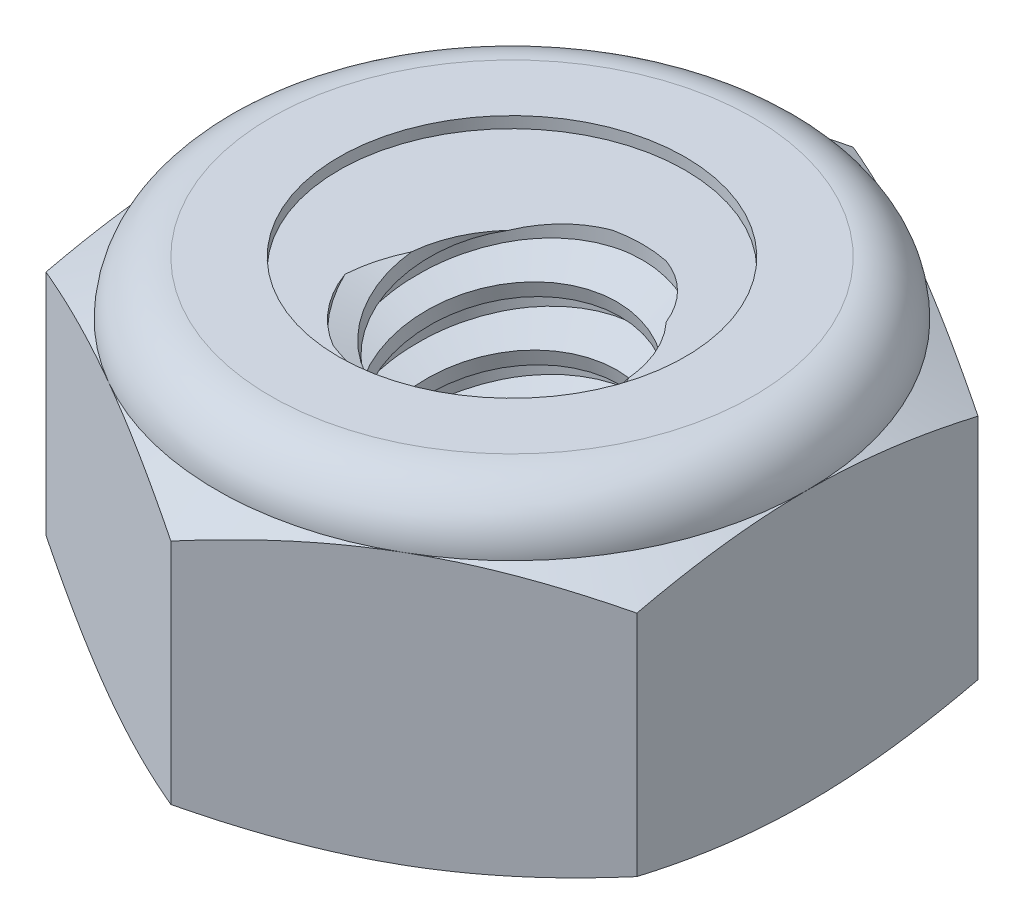
SolidWorks part; units mm, degrees
ref_plane "Front" through (0, 0, 0) normal (0, 0, 1) x (1, 0, 0)
ref_plane "Top" through (0, 0, 0) normal (0, 1, 0) x (1, 0, 0)
ref_plane "Right" through (0, 0, 0) normal (1, 0, 0) x (0, 0, -1)
sketch "Sketch1" plane through (0, 0, 0) normal (0, 1, 0) x (1, 0, 0)
  line L1 (0, 4.5827) -> (-3.9688, 2.2914)
  line L2 (-3.9688, 2.2914) -> (-3.9688, -2.2914)
  line L3 (-3.9688, -2.2914) -> (0, -4.5827)
  line L4 (0, -4.5827) -> (3.9687, -2.2914)
  line L5 (3.9687, -2.2914) -> (3.9687, 2.2914)
  line L6 (3.9687, 2.2914) -> (0, 4.5827)
  circle A0 centre (0, 0) radius 3.9688 construction
  dimension "Hex Flats" = 7.9375
extrude "Extrude1" add sketch "Sketch1" along normal blind 4.3656
sketch "Sketch2" plane through (0, 0, 0) normal (1, 0, 0) x (0, 0, -1)
  line L0 (-1.7526, 0) -> (-1.7526, 4.3656) construction
  line L1 (0, 0) -> (1.7526, 0)
  line L2 (0, 0) -> (0, 4.3656)
  line L3 (0, 4.3656) -> (1.7526, 4.3656)
  line L4 (1.7526, 0) -> (1.7526, 4.3656)
  line L5 (-2.2914, 4.3656) -> (2.2914, 4.3656) construction
  line L7 (0, -1.7526) -> (0, 0) construction
  dimension "Thread Dia" = 3.5052
revolve "Revolve1" add sketch "Sketch2" angle 360 about L7
sketch "Sketch3" plane through (0, 0, 0) normal (1, 0, 0) x (0, 0, -1)
  line L0 (1.7526, 4.3656) -> (-1.7526, 4.3656) construction
  line L1 (-1.7526, 4.3656) -> (-1.7526, 3.5719) construction
  line L2 (-1.7526, 3.5719) -> (1.7526, 4.3656) construction
  line L3 (1.7526, 4.3656) -> (1.7745, 4.2689) construction
  line L4 (1.7745, 4.2689) -> (1.9279, 3.5915)
  line L5 (1.9279, 3.5915) -> (1.4541, 3.7385)
  line L6 (1.4541, 3.7385) -> (1.4103, 3.932)
  line L7 (1.4103, 3.932) -> (1.7745, 4.2689)
  line L8 (1.4322, 3.8353) -> (1.8512, 3.9302) construction
  line L9 (1.7526, 4.3656) -> (1.7526, 3.9078) construction
  line L10 (1.7526, 3.9078) -> (-1.7526, 3.1141) construction
  line L11 (-1.7526, 3.1141) -> (-1.7526, 3.5719) construction
  line L12 (-0.1935, 4.3656) -> (0.1935, 2.6563) construction
  line L13 (-1.7526, 0) -> (-1.7526, 4.3656) construction
  line L14 (0, 4.3656) -> (1.7526, 4.3656) construction
  line L15 (1.7526, 0) -> (1.7526, 4.3656) construction
  point P13 (0, 3.511)
  dimension "D1" = 0.0992
  dimension "D2" = 0.1984
  dimension "Thread Pitch" = 0.7937
  dimension "D4" = 60
  dimension "D5" = 0.7937
revolve "Cut-Revolve1" cut sketch "Sketch3" angle 360 about L12
pattern_linear "LPattern1" count 6 spacing 0.7937 along (0, -1, 0) count 2 spacing 0.7937 along (0, 1, 0) of "Cut-Revolve1"
sketch "Sketch4" plane through (0, 0, 0) normal (1, 0, 0) x (0, 0, -1)
  line L0 (0, 4.3656) -> (1.7526, 4.3656)
  line L1 (1.7526, 4.3656) -> (1.4103, 4.206)
  line L2 (1.4103, 4.206) -> (1.4103, 0.1596)
  line L3 (1.4103, 0.1596) -> (1.7526, 0)
  line L4 (1.7526, 0) -> (0, 0)
  line L5 (0, 0) -> (0, 4.3656)
  line L6 (1.7526, 0) -> (1.7526, 4.3656) construction
  line L7 (0, 4.3656) -> (1.7526, 4.3656) construction
  line L8 (0, 0) -> (1.7526, 0) construction
  line L9 (0, 0) -> (0, 4.3656) construction
  line L10 (0, 4.3656) -> (0, 4.7433) construction
  dimension "D1" = 25
combine bodies "Combine1" operation type subtract main body 108 bodies to subtract 111
sketch "Sketch5" plane through (0, 0, 0) normal (1, 0, 0) x (0, 0, -1)
  line L0 (0, 0) -> (3.9688, 0)
  line L1 (3.9688, 0) -> (4.5827, 0.2863)
  line L2 (4.5827, 0.2863) -> (4.5827, 3.3517)
  line L3 (4.5827, 3.3517) -> (3.9688, 3.638)
  line L4 (3.2411, 4.3656) -> (3.2411, 5.6356)
  line L5 (3.2411, 5.6356) -> (5.8527, 5.6356)
  line L6 (5.8527, 5.6356) -> (5.8527, -1.27)
  line L7 (5.8527, -1.27) -> (0, -1.27)
  line L8 (0, -1.27) -> (0, 0)
  line L9 (3.9688, 3.638) -> (3.9688, 0) construction
  line L10 (0, 0) -> (1.7526, 0) construction
  line L13 (4.5827, 1.819) -> (5.8527, 1.819) construction
  line L14 (4.5827, 4.3656) -> (4.5827, 0) construction
  line L15 (0, 0) -> (0, 5.6356) construction
  line L20 (0, 5.6356) -> (3.2411, 5.6356) construction
  line L22 (0, 4.3656) -> (1.7526, 4.3656) construction
  arc A0 (3.9688, 3.638) -> (3.2411, 4.3656) centre (3.2411, 3.638) ccw
  dimension "D1" = 25
  dimension "D2" = 1.27
  dimension "D3" = 4.3656
  dimension "D4" = 0.7276
revolve "Cut-Revolve3" cut sketch "Sketch5" angle 360 about L15
sketch "Sketch6" plane through (0, 0, 0) normal (1, 0, 0) x (0, 0, -1)
  line L0 (0, 3.638) -> (3.8164, 3.638)
  line L1 (3.2411, 4.2132) -> (2.3257, 4.2132)
  line L2 (0, 5.6356) -> (0, 3.638)
  line L3 (2.3257, 5.6356) -> (0, 5.6356)
  line L4 (0, 5.6356) -> (3.2411, 5.6356) construction
  line L5 (0, 0) -> (0, 5.6356) construction
  line L6 (0, 5.6356) -> (0, 44.323) construction
  line L7 (2.3257, 4.2132) -> (2.3257, 5.6356)
  line L8 (3.2411, 4.3656) -> (3.2411, 4.2132) construction
  line L9 (2.3257, 4.2132) -> (1.4103, 4.2132) construction
  line L10 (1.4103, 4.2132) -> (1.4103, 4.206) construction
  arc A0 (3.8164, 3.638) -> (3.2411, 4.2132) centre (3.2411, 3.638) ccw
  arc A1 (3.9688, 3.638) -> (3.2411, 4.3656) centre (3.2411, 3.638) ccw construction
  dimension "D1" = 0.1524
revolve "Cut-Revolve4" cut sketch "Sketch6" angle 360 about L6
sketch "Sketch7" plane through (0, 0, 0) normal (1, 0, 0) x (0, 0, -1)
  line L0 (1.4103, 3.7142) -> (3.7343, 3.7142)
  line L1 (3.2411, 4.137) -> (1.4103, 4.137)
  line L2 (1.4103, 4.137) -> (1.4103, 3.7142)
  line L3 (1.4103, 3.7142) -> (0, 3.7142) construction
  line L4 (0, 3.7142) -> (0, 4.137) construction
  line L5 (0, 4.137) -> (1.4103, 4.137) construction
  line L6 (1.4103, 3.7142) -> (1.4103, 3.638) construction
  line L7 (0, 3.638) -> (3.8164, 3.638) construction
  line L8 (3.2411, 4.137) -> (3.2411, 4.2132) construction
  arc A0 (3.7343, 3.7142) -> (3.2411, 4.137) centre (3.2411, 3.638) ccw
  arc A2 (3.8164, 3.638) -> (3.2411, 4.2132) centre (3.2411, 3.638) ccw construction
  dimension "D1" = 0.0762
equation "\"D1@Sketch3\"=\"Thread Pitch@Sketch3\"/8"
equation "\"D2@Sketch3\"=\"Thread Pitch@Sketch3\"/4"
equation "\"D5@Sketch3\"=\"Thread Pitch@Sketch3\""
equation "\"D4@LPattern1\"=\"Thread Pitch@Sketch3\""
equation "\"D3@LPattern1\"=\"Thread Pitch@Sketch3\""
equation "\"D1@LPattern1\"=\"Height@Extrude1\"/\"Thread Pitch@Sketch3\""
equation "\"D4@Sketch5\"=\"Height@Extrude1\"/6"
